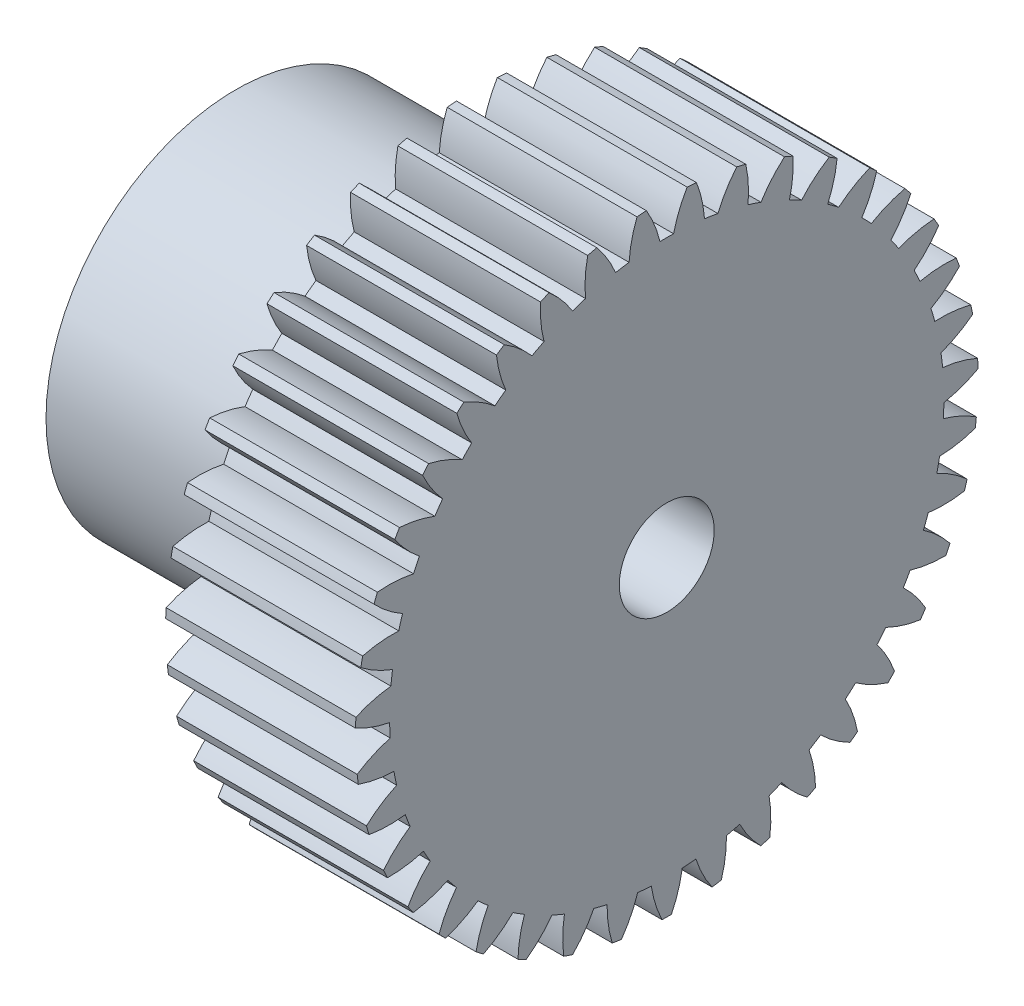
SolidWorks part; units mm, degrees
ref_plane "Plane1" through (0, 0, 0) normal (0, 0, 1) x (1, 0, 0)
ref_plane "Plane2" through (0, 0, 0) normal (0, 1, 0) x (1, 0, 0)
ref_plane "Plane3" through (0, 0, 0) normal (1, 0, 0) x (0, 0, -1)
sketch "HoldingSke" plane through (0, 0, 0) normal (0, 1, 0) x (1, 0, 0)
  line L0 (0, 0) -> (0.9714, -0.7867)
  line L1 (-15, 0) -> (100, 0) construction
  line L2 (0, 0) -> (-2.1039, 2.3779)
  line L3 (0, 0) -> (-11.863, 4.5341)
  line L4 (0, 0) -> (6.7114, 5.4348)
  line L5 (0, 0) -> (-9.3695, -3.4946)
  line L6 (0, 0) -> (-8.2896, -5.593)
  line L7 (-2.1039, 2.3779) -> (0.0486, 12.1435)
  line L8 (-76.2, 54.61) -> (-75.3, 54.61)
  line L9 (-71.009, 38.7566) -> (-53.1078, 45.2721)
  line L10 (-76.2, 71.12) -> (104.1128, 71.12)
  line L11 (0, 0) -> (-10, 0)
  line L12 (-76.2, 101.6) -> (-76.17, 101.6)
  line L13 (24.9733, 27.94) -> (52.9518, 28.4284)
  line L14 (24.9733, 27.94) -> (24.9743, 27.94)
  line L15 (24.9733, 27.94) -> (100.4006, 29.5858)
  line L16 (-63.627, -0.8) -> (-12.827, -0.8)
  circle A0 centre (0, 0) radius 2.5
  circle A1 centre (0, 0) radius 10
  circle A2 centre (0, 0) radius 10
  circle A3 centre (0, 0) radius 2.5
  dimension "Num_teeth" = 39
  dimension "Pitch_radius" = 180.3128
  dimension "Width" = 10
  dimension "Thickness" = 10
sketch "BasProSke" plane through (0, 0, 0) normal (0, 1, 0) x (1, 0, 0)
  line L0 (-10, 0) -> (60, 0) construction
  line L1 (0, 0) -> (0, 16.4)
  line L2 (0, 0) -> (10, 0)
  line L3 (10, 0) -> (10, 16.4)
  line L4 (10, 16.4) -> (0, 16.4)
  dimension "Thickness" = 10
  dimension "Diameter" = 32.8
revolve "Base-Revolve" add sketch "BasProSke" angle 360 about L0
sketch "TooCutSke" plane through (0, 0, 0) normal (1, 0, 0) x (0, 0, -1)
  line L1 (0, 0) -> (0, 107) construction
  line L2 (0, 0) -> (-0.6806, 15.5851) construction
  line L3 (0, 0) -> (-2.5088, 31.0776) construction
  line L4 (-0.6806, 15.5851) -> (-1.2544, 15.5388) construction
  arc A0 (0.3593, 14.5946) -> (-0.3593, 14.5946) centre (0, 0) ccw
  arc A1 (1.0886, 16.3893) -> (-1.0886, 16.3893) centre (0, 0) ccw
  circle A2 centre (0, 0) radius 15.6 construction
  circle A3 centre (0, 0) radius 14.6592 construction
  arc A4 (-0.3593, 14.5946) -> (-1.0886, 16.3893) centre (-6.4349, 13.1714) ccw
  arc A5 (1.0886, 16.3893) -> (0.3593, 14.5946) centre (6.4349, 13.1714) ccw
extrude "ToothCut" cut sketch "TooCutSke" along normal through all
fillet "Breaks" [suppressed] radius 0.016 tangent propagation no
fillet "RootFillets" [suppressed] radius 0.201
pattern_circular "TeethCuts" count 39 every 9.231 about axis through (-10, 0, 0) along (1, 0, 0) of "ToothCut", "RootFillets", "Breaks"
sketch "HubNeaOneSke" plane through (0, 0, 0) normal (-1, 0, 0) x (0, 0, 1)
  circle A0 centre (0, 0) radius 10
  dimension "Diameter" = 20
extrude "HubNearOne" add sketch "HubNeaOneSke" along normal blind 12.7001
sketch "HubNeaBotSke" plane through (0, 0, 0) normal (-1, 0, 0) x (0, 0, 1)
  circle A0 centre (0, 0) radius 10
  dimension "Diameter" = 20
extrude "HubNearBoth" [suppressed] add sketch "HubNeaBotSke" along normal blind 6.35
ref_plane "FarPln" through (10, 0, 0) normal (1, 0, 0) x (0, 0, -1)
sketch "HubFarSke" plane through (10, 0, 0) normal (1, 0, 0) x (0, 0, -1)
  circle A0 centre (0, 0) radius 10
  dimension "Diameter" = 20
extrude "HubFar" [suppressed] add sketch "HubFarSke" along normal blind 6.35
sketch "BorSke" plane through (0, 0, 0) normal (1, 0, 0) x (0, 0, -1)
  circle A0 centre (0, 0) radius 2.5
  dimension "Diameter" = 5
extrude "Bore" cut sketch "BorSke" along normal mid plane 20.0001
sketch "KeySke" plane through (0, 0, 0) normal (1, 0, 0) x (0, 0, -1)
  line L0 (-1, 0) -> (-1, 3.4)
  line L1 (-1, 3.4) -> (1, 3.4)
  line L2 (1, 3.4) -> (1, 0)
  line L3 (0, 0) -> (0, 34) construction
  line L4 (-1, 0) -> (1, 0)
  dimension "Width" = 2
extrude "Keyway" [suppressed] cut sketch "KeySke" along normal mid plane 20.0001
pattern_circular "Keyway2" [suppressed] count 2 every 90 about axis through (-10, 0, 0) along (1, 0, 0) reverse direction yes
equation "' \"Module@HoldingSke\" = 6.35"
equation "' \"Num_teeth@HoldingSke\" = 12"
equation "' \"Ap@HoldingSke\" =  20"
equation "' \"Ap@HoldingSke\" = 20"
equation "' \"Width@HoldingSke\" = 0.5 * 25.4"
equation "' \"Hub_dia@HoldingSke\"= 1 * 25.4"
equation "' \"Hub_dia@HoldingSke\" = 1 * 25.4"
equation "' \"Overall_len@HoldingSke\" = 1.0 * 25.4"
equation "' \"Bore@HoldingSke\" = 0.75 * 25.4"
equation "' \"T_dim@HoldingSke\" = 0.1 * 25.4"
equation "' \"Width@KeySke\" = 0.25 * 25.4"
equation "' \"Show_teeth@HoldingSke\" = 13"
equation "' \"Backlash@HoldingSke\" = 0.009 * 25.4"
equation "' \"Addendum_fac@HoldingSke\" = 1.0"
equation "' \"Dedendum_fac@HoldingSke\" = 1.25"
equation "' \"Dedendum_add@HoldingSke\" = 0.00005 * 25.4"
equation "' \"Clearance_fac@HoldingSke\" = 0.25"
equation "\"Pitch@HoldingSke\" = 1 / \"Module@HoldingSke\""
equation "\"Overcut_dia@TooCutSke\" = (\"Num_teeth@HoldingSke\" + 2 * \"Addendum_fac@HoldingSke\") / \"Pitch@HoldingSke\" + 0.002 * 25.4"
equation "\"Pitch_dia@TooCutSke\" = \"Num_teeth@HoldingSke\" / \"Pitch@HoldingSke\""
equation "\"Base_dia@TooCutSke\" = \"Num_teeth@HoldingSke\" / \"Pitch@HoldingSke\" * cos((\"Ap@HoldingSke\"  * 3.14159265 / 180))"
equation "\"Root_dia@TooCutSke\" = (\"Num_teeth@HoldingSke\" + 2) / \"Pitch@HoldingSke\" - 2 * (\"Addendum_fac@HoldingSke\" + \"Dedendum_fac@HoldingSke\") / \"Pitch@HoldingSke\" - \"Dedendum_add@HoldingSke\" * 2"
equation "\"Half_ang@TooCutSke\" = 180 / \"Num_teeth@HoldingSke\""
equation "\"Half_CT@TooCutSke\" = \"Num_teeth@HoldingSke\" / \"Pitch@HoldingSke\" * sin((3.14159265 / 2 / \"Num_teeth@HoldingSke\")) / 2 - 7 * \"Backlash@HoldingSke\" / 4"
equation "\"Flank_rad@TooCutSke\" = \"Num_teeth@HoldingSke\" / \"Pitch@HoldingSke\" / 5"
equation "\"Radius@RootFillets\" = \"Clearance_fac@HoldingSke\" / \"Pitch@HoldingSke\" + \"Dedendum_add@HoldingSke\""
equation "\"Break_rad@Breaks\" = 0.02 / \"Pitch@HoldingSke\""
equation "\"Thickness@HoldingSke\" = \"Width@HoldingSke\""
equation "\"OAL@HoldingSke\" = \"Thickness@HoldingSke\""
equation "\"MHD@HoldingSke\" = (\"Num_teeth@HoldingSke\" + 2) / \"Pitch@HoldingSke\" - 2 * (\"Addendum_fac@HoldingSke\" + \"Dedendum_fac@HoldingSke\")  / \"Pitch@HoldingSke\" - \"Dedendum_add@HoldingSke\" * 2"
equation "\"MBD@HoldingSke\" = (\"Num_teeth@HoldingSke\" + 2) / \"Pitch@HoldingSke\" - 2 * (\"Addendum_fac@HoldingSke\" + \"Dedendum_fac@HoldingSke\")  / \"Pitch@HoldingSke\" - \"Dedendum_add@HoldingSke\" * 2 - 0.002 * 25.4"
equation "\"MHD@HoldingSke\" = ((sgn( \"MHD@HoldingSke\" - \"Hub_dia@HoldingSke\" )-1)*( \"MHD@HoldingSke\" - \"Hub_dia@HoldingSke\" ))/-2+ \"Hub_dia@HoldingSke\""
equation "\"MBD@HoldingSke\" = ((sgn( \"MBD@HoldingSke\" - \"Bore@HoldingSke\" )-1)*( \"MBD@HoldingSke\" - \"Bore@HoldingSke\" ))/-2+ \"Bore@HoldingSke\""
equation "\"OAL@HoldingSke\" = ((sgn( \"OAL@HoldingSke\" - \"Overall_len@HoldingSke\" )+1)*( \"OAL@HoldingSke\" - \"Overall_len@HoldingSke\" ))/2 + \"Overall_len@HoldingSke\" + 0.000002 * 25.4"
equation "\"Num_teeth@TeethCuts\" = int( \"Show_teeth@HoldingSke\" ) + 1"
equation "\"Num_teeth@TeethCuts\" = ((sgn( \"Num_teeth@TeethCuts\" - \"Num_teeth@HoldingSke\" )-1)*( \"Num_teeth@TeethCuts\" - \"Num_teeth@HoldingSke\" ))/-2+ \"Num_teeth@HoldingSke\""
equation "\"Num_teeth@TeethCuts\" = ((sgn( \"Num_teeth@TeethCuts\" - 2.0)+1)*( \"Num_teeth@TeethCuts\" - 2.0))/2 +2.0"
equation "\"Angle@TeethCuts\" = 360.0 / \"Num_teeth@HoldingSke\""
equation "\"Diameter@BasProSke\" = (\"Num_teeth@HoldingSke\" + 2 * \"Addendum_fac@HoldingSke\") / \"Pitch@HoldingSke\""
equation "\"Thickness@BasProSke\"  = \"Thickness@HoldingSke\""
equation "' \"Fillet_rad@BasProSke\" =  \"Thickness@HoldingSke\" * 0.05"
equation "' \"Fillet_rad@BasProSke\" = \"Thickness@HoldingSke\" * 0.05"
equation "\"MHD@HoldingSke\" = ((sgn( \"MHD@HoldingSke\" - \"Root_dia@TooCutSke\" )-1)*( \"MHD@HoldingSke\" - \"Root_dia@TooCutSke\" ))/-2+ \"Root_dia@TooCutSke\""
equation "\"Diameter@HubNeaOneSke\" = \"MHD@HoldingSke\""
equation "\"Length@HubNearOne\" = \"OAL@HoldingSke\" - \"Thickness@BasProSke\""
equation "\"Diameter@HubNeaBotSke\" = \"MHD@HoldingSke\""
equation "\"Length@HubNearBoth\" = ( \"OAL@HoldingSke\" - \"Thickness@BasProSke\" ) / 2.0"
equation "\"Thickness@FarPln\" = \"Thickness@BasProSke\""
equation "\"Diameter@HubFarSke\" = \"MHD@HoldingSke\""
equation "\"Length@HubFar\" = ( \"OAL@HoldingSke\" - \"Thickness@BasProSke\" ) / 2.0"
equation "\"Diameter@BorSke\" = \"MBD@HoldingSke\""
equation "\"D1@Bore\" = \"OAL@HoldingSke\" * 2.0"
equation "\"D1@Keyway\" = \"OAL@HoldingSke\" * 2.0"
equation "\"Offset@KeySke\" = \"T_dim@HoldingSke\" + \"MBD@HoldingSke\" / 2.0"
